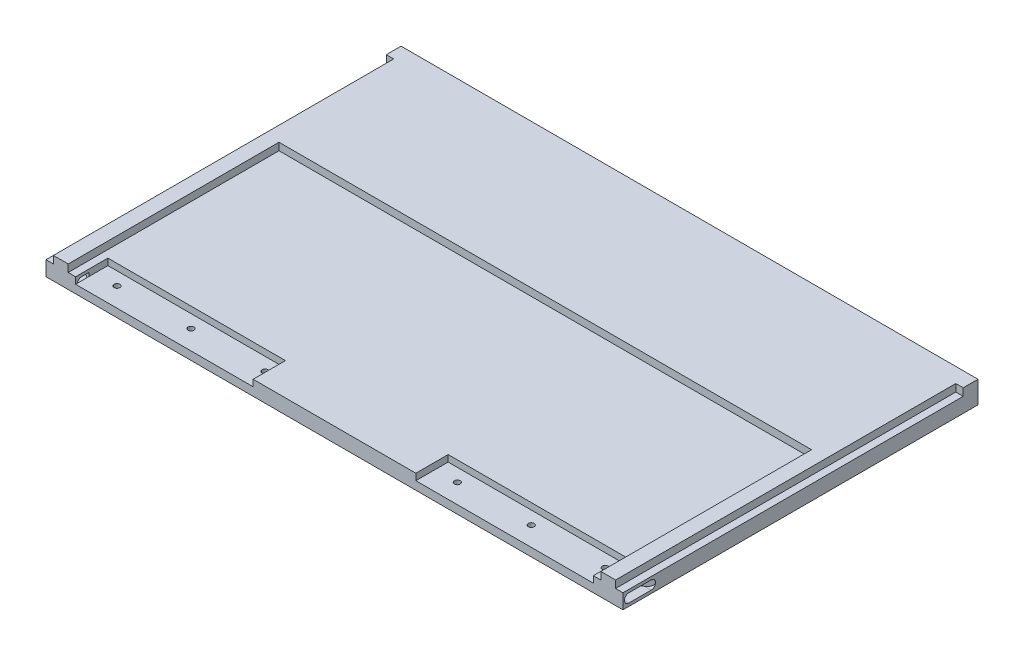
SolidWorks part; units mm, degrees
other "Markup1"
sketch "Sketch12" plane through (250.825, 22.225, 158.75) normal (0.1153, 0.0728, 0.9907) x (0.9687, -0.2289, -0.0959)
material "6061 Alloy"
ref_plane "Front Plane" through (0, 0, 0) normal (0, 0, 1) x (1, 0, 0)
ref_plane "Top Plane" through (0, 0, 0) normal (0, 1, 0) x (1, 0, 0)
ref_plane "Right Plane" through (0, 0, 0) normal (1, 0, 0) x (0, 0, -1)
sketch "Sketch1" plane through (0, 0, 0) normal (0, 1, 0) x (1, 0, 0)
  line L1 (-241.3, 152.4) -> (241.3, 152.4)
  line L2 (-241.3, 152.4) -> (-241.3, -152.4)
  line L3 (-241.3, -152.4) -> (241.3, -152.4)
  line L4 (241.3, 152.4) -> (241.3, -152.4)
  line L5 (-241.3, 152.4) -> (241.3, -152.4) construction
  line L6 (-241.3, -152.4) -> (241.3, 152.4) construction
  circle A0 centre (-203.2, -135.8392) radius 2.5019 construction
  circle A1 centre (-139.7, -135.8392) radius 2.5019 construction
  circle A2 centre (-76.2, -135.8392) radius 2.5019 construction
  circle A3 centre (88.9, -135.8392) radius 2.5019 construction
  circle A4 centre (152.4, -135.8392) radius 2.5019 construction
  circle A5 centre (215.9, -135.8392) radius 2.5019 construction
  circle A6 centre (-203.2, -135.8392) radius 2.5019
  circle A7 centre (-139.7, -135.8392) radius 2.5019
  circle A8 centre (-76.2, -135.8392) radius 2.5019
  circle A9 centre (88.9, -135.8392) radius 2.5019
  circle A10 centre (152.4, -135.8392) radius 2.5019
  circle A11 centre (215.9, -135.8392) radius 2.5019
  point P0 (0, 0)
  dimension "D1" = 482.6
  dimension "D2" = 304.8
extrude "Boss-Extrude1" add sketch "Sketch1" along normal blind 12.7
sketch "Sketch2" plane through (0, 12.7, 0) normal (0, 1, 0) x (1, 0, 0)
  line L0 (-241.3, -152.4) -> (241.3, -152.4) construction
  line L1 (-241.3, 152.4) -> (-228.6, 152.4)
  line L2 (-241.3, 152.4) -> (-241.3, -152.4)
  line L3 (-241.3, -152.4) -> (-228.6, -152.4)
  line L4 (-228.6, 28.575) -> (-228.6, -152.4)
  line L5 (241.3, 152.4) -> (-241.3, 152.4) construction
  line L6 (241.3, 152.4) -> (228.6, 152.4)
  line L7 (241.3, 152.4) -> (241.3, -152.4)
  line L8 (241.3, -152.4) -> (228.6, -152.4)
  line L9 (228.6, 28.575) -> (228.6, -152.4)
  line L10 (-228.6, 152.4) -> (228.6, 152.4)
  line L12 (-228.6, 28.575) -> (228.6, 28.575)
  point P14 (-234.95, -152.4)
  dimension "D1" = 12.7
  dimension "D2" = 180.975
extrude "Boss-Extrude2" add sketch "Sketch2" along normal blind 6.35
sketch "Sketch3" plane through (-241.3, 0, 0) normal (-1, 0, 0) x (0, 0, 1)
  line L0 (152.4, 19.05) -> (152.4, 0) construction
  line L1 (-152.4, 19.05) -> (152.4, 19.05) construction
  circle A0 centre (149.225, 15.875) radius 1.5875
  dimension "D3" = 3.175
  dimension "D1" = 3.175
  dimension "D2" = 3.175
sketch "Sketch4" plane through (0, 0, 152.4) normal (0, 0, 1) x (1, 0, 0)
  line L0 (-241.3, 19.05) -> (-241.3, 0) construction
  line L1 (-241.3, 12.7) -> (-247.65, 12.7)
  line L2 (-241.3, 12.7) -> (-241.3, 0)
  line L3 (-241.3, 0) -> (-247.65, 0)
  line L4 (-247.65, 12.7) -> (-247.65, 0)
  line L5 (-241.3, 0) -> (241.3, 0) construction
  dimension "D1" = 12.7
  dimension "D2" = 6.35
extrude "Boss-Extrude3" add sketch "Sketch4" against normal blind 292.1
sketch "Sketch5" plane through (-241.3, 0, 0) normal (-1, 0, 0) x (0, 0, 1)
  line L0 (-152.4, 0) -> (-139.7, 0) construction
  line L1 (-152.4, 19.05) -> (-139.7, 19.05)
  line L2 (-152.4, 19.05) -> (-152.4, 0)
  line L3 (-152.4, 0) -> (-139.7, 0)
  line L4 (-139.7, 19.05) -> (-139.7, 0)
  line L5 (-139.7, 0) -> (-139.7, 12.7) construction
extrude "Boss-Extrude4" add sketch "Sketch5" along normal up to surface (6.35 mm away) up to face at (-247.65, 6.35, 6.35)
mirror "Mirror1" about plane through (0, 0, 0) normal (1, 0, 0) of "Boss-Extrude4", "Boss-Extrude3"
sketch "Sketch6" plane through (-241.3, 0, 0) normal (-1, 0, 0) x (0, 0, 1)
  line L0 (147.32, 6.35) -> (128.27, 6.35) construction
  line L1 (147.32, 2.54) -> (128.27, 2.54)
  line L2 (147.32, 10.16) -> (128.27, 10.16)
  line L3 (152.4, 19.05) -> (152.4, 12.7) construction
  line L5 (152.4, 12.7) -> (152.4, 0) construction
  arc A0 (147.32, 2.54) -> (147.32, 10.16) centre (147.32, 6.35) ccw
  arc A1 (128.27, 10.16) -> (128.27, 2.54) centre (128.27, 6.35) ccw
  point P2 (137.795, 6.35)
  point P11 (152.4, 6.35)
  dimension "D1" = 19.05
  dimension "D2" = 5.08
  dimension "D3" = 7.62
extrude "Cut-Extrude2" cut sketch "Sketch6" against normal blind 25.4 from surface starting at face at (-247.65, 10.5833, -46.5667)
extrude "Cut-Extrude3" cut sketch "Sketch6<2>" along normal blind 25.4 from surface starting at face at (247.65, 10.5833, -46.5667)
sketch "Sketch6<2>" plane through (-241.3, 0, 0) normal (-1, 0, 0) x (0, 0, 1) same geometry as "Sketch6"
sketch "Sketch11" plane through (0, 0, 0) normal (0, -1, 0) x (1, 0, 0)
  line L0 (-247.65, 124.46) -> (-222.25, 124.46)
  line L1 (-222.25, 124.46) -> (-222.25, 140.97)
  line L2 (-222.25, 140.97) -> (-247.65, 124.46)
  line L3 (-222.25, 128.27) -> (-222.25, 147.32) construction
  dimension "D1" = 10.16
extrude "Boss-Extrude5" add sketch "Sketch11" against normal up to surface (10.16 mm away) from surface up to face at (-234.95, 10.16, 137.795) starting at face at (-234.95, 2.54, 137.795)
mirror "Mirror2" about plane through (0, 0, 0) normal (1, 0, 0) of "Boss-Extrude5"
sketch "Sketch13" plane through (0, 12.7, 0) normal (0, 1, 0) x (1, 0, 0)
  line L0 (228.6, 28.575) -> (228.6, -152.4) construction
  line L1 (222.25, -152.4) -> (69.85, -152.4)
  line L2 (222.25, -152.4) -> (222.25, -124.6632)
  line L3 (222.25, -124.6632) -> (69.85, -124.6632)
  line L4 (69.85, -152.4) -> (69.85, -124.6632)
  line L5 (-228.6, -152.4) -> (228.6, -152.4) construction
  line L6 (0, 0) -> (0, -222.4022) construction
  line L7 (-222.25, -152.4) -> (-222.25, -124.6632)
  line L8 (-222.25, -152.4) -> (-69.85, -152.4)
  line L9 (-69.85, -152.4) -> (-69.85, -124.6632)
  line L10 (-222.25, -124.6632) -> (-69.85, -124.6632)
  dimension "D1" = 27.7368
  dimension "D2" = 6.35
  dimension "D3" = 152.4
extrude "Cut-Extrude4" cut sketch "Sketch13" against normal blind 5.588
